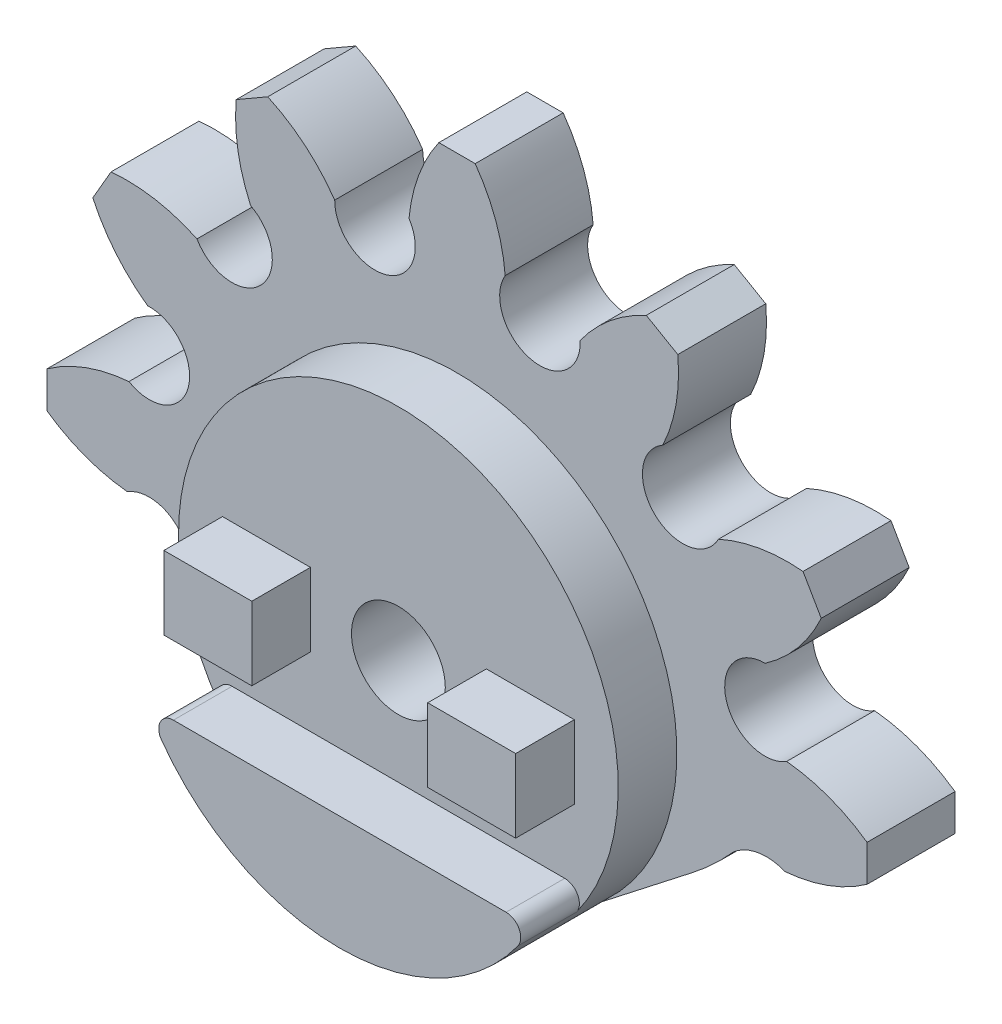
SolidWorks part; units mm, degrees
material "PLA"
ref_plane "Front Plane" through (0, 0, 0) normal (0, 0, 1) x (1, 0, 0)
ref_plane "Top Plane" through (0, 0, 0) normal (0, 1, 0) x (1, 0, 0)
ref_plane "Right Plane" through (0, 0, 0) normal (1, 0, 0) x (0, 0, -1)
other "Graphic1"
other "Graphic (Closed) -1"
sketch "Sketch1" plane through (0, 0, 0) normal (0, 0, 1) x (1, 0, 0)
  line L0 (0.1538, 8.164) -> (0.1538, 6.9226)
  line L1 (6.1332, 4.2732) -> (9.5312, 1.6264)
  line L2 (2.3379, 15.0739) -> (1.7172, 13.9988)
  line L3 (7.6844, 19.966) -> (6.6093, 19.3453)
  line L4 (14.7607, 21.5295) -> (13.5193, 21.5295)
  line L5 (21.6707, 19.3453) -> (20.5956, 19.966)
  line L6 (26.5628, 13.9988) -> (25.9421, 15.0739)
  line L7 (28.1262, 6.9226) -> (28.1262, 8.164)
  line L9 (22.1468, 4.2732) -> (18.7488, 1.6264)
  line L13 (1.7172, 1.0877) -> (2.3379, 0.0126) [skipped]
  line L14 (6.6093, -4.2588) -> (7.6844, -4.8795) [skipped]
  line L15 (20.5956, -4.8795) -> (21.6707, -4.2588) [skipped]
  line L16 (25.9421, 0.0126) -> (26.5628, 1.0877) [skipped]
  line L17 (13.5193, -6.443) -> (14.7607, -6.443) [skipped]
  circle A0 centre (14.14, 7.5433) radius 1.6
  arc A1 (9.5312, 1.6264) -> (18.7488, 1.6264) centre (14.14, 7.5433) ccw
  arc A2 (0.1538, 6.9226) -> (2.9496, 5.9002) centre (3.4462, 11.5926) ccw
  arc A3 (2.9496, 5.9002) -> (4.7183, 5.5952) centre (3.5857, 4.3084) cw
  arc A4 (4.7183, 5.5952) -> (6.1332, 4.2732) centre (12.2208, 12.2067) ccw
  arc A5 (0.1538, 8.164) -> (2.9496, 9.1863) centre (3.4106, 3.5913) cw
  arc A6 (2.9496, 9.1863) -> (3.5736, 11.7455) centre (3.644, 10.3727) ccw
  arc A7 (5.2703, 14.5613) -> (7.0904, 16.4657) centre (6.4649, 15.2416) ccw
  arc A8 (2.3379, 15.0739) -> (5.2703, 14.5613) centre (2.8721, 9.4855) cw
  arc A9 (1.7172, 13.9988) -> (3.6273, 11.7156) centre (6.9036, 16.397) ccw
  arc A10 (9.9677, 18.0559) -> (12.4961, 18.7951) centre (11.3423, 18.0478) ccw
  arc A11 (7.6844, 19.966) -> (9.9677, 18.0559) centre (5.3528, 14.8592) cw
  arc A12 (6.6093, 19.3453) -> (7.1219, 16.4129) centre (12.3, 18.829) ccw
  arc A13 (15.783, 18.7336) -> (18.3422, 18.1096) centre (16.9694, 18.0393) ccw
  arc A14 (14.7607, 21.5295) -> (15.783, 18.7336) centre (10.1881, 18.2727) cw
  arc A15 (13.5193, 21.5295) -> (12.497, 18.7336) centre (18.1894, 18.237) ccw
  arc A16 (21.1581, 16.4129) -> (23.0624, 14.5929) centre (21.8384, 15.2184) ccw
  arc A17 (21.6707, 19.3453) -> (21.1581, 16.4129) centre (16.0822, 18.8112) cw
  arc A18 (20.5956, 19.966) -> (18.3123, 18.0559) centre (22.9937, 14.7797) ccw
  arc A19 (24.6527, 11.7156) -> (25.3919, 9.1872) centre (24.6445, 10.3409) ccw
  arc A20 (26.5628, 13.9988) -> (24.6527, 11.7156) centre (21.456, 16.3304) cw
  arc A21 (25.9421, 15.0739) -> (23.0097, 14.5613) centre (25.4258, 9.3833) ccw
  arc A22 (24.6957, 3.3405) -> (24.7064, 3.341) centre (24.636, 4.7139) ccw
  arc A23 (28.1262, 6.9226) -> (25.3304, 5.9002) centre (24.8694, 11.4952) cw
  arc A24 (28.1262, 8.164) -> (25.3304, 9.1863) centre (24.8338, 3.4939) ccw
  arc A25 (21.1802, -1.3743) -> (21.1896, -1.3792) centre (21.8151, -0.1551) ccw
  arc A26 (23.5617, 5.5952) -> (22.1468, 4.2732) centre (16.0592, 12.2067) cw
  arc A27 (24.6957, 3.3405) -> (24.6527, 3.371) centre (21.3764, -1.3105) ccw
  arc A28 (15.7782, -3.6997) -> (15.7839, -3.7086) centre (16.9377, -2.9613) ccw
  arc A29 (25.3304, 5.9002) -> (23.5617, 5.5952) centre (24.6943, 4.3084) ccw
  arc A30 (21.1802, -1.3743) -> (21.1581, -1.3264) centre (15.98, -3.7425) ccw
  arc A31 (9.9373, -3.0125) -> (9.9378, -3.0231) centre (11.3106, -2.9528) ccw
  arc A33 (15.7782, -3.6997) -> (15.783, -3.6471) centre (10.0906, -3.1505) ccw
  arc A34 (5.2224, 0.5031) -> (5.2176, 0.4936) centre (6.4416, -0.1319) ccw
  arc A36 (9.9373, -3.0125) -> (9.9677, -2.9694) centre (5.2863, 0.3068) ccw
  arc A37 (4.7111, 5.6016) -> (2.8881, 5.8993) centre (3.6355, 4.7456) ccw
  arc A39 (5.2224, 0.5031) -> (5.2703, 0.5252) centre (2.8542, 5.7032) ccw
  arc A40 (1.7172, 1.0877) -> (3.6273, 3.371) centre (6.824, -1.2439) cw [skipped]
  arc A41 (6.6093, -4.2588) -> (7.1219, -1.3264) centre (12.1978, -3.7246) cw [skipped]
  arc A42 (13.5193, -6.443) -> (12.497, -3.6471) centre (18.0919, -3.1861) cw [skipped]
  arc A43 (20.5956, -4.8795) -> (18.3123, -2.9694) centre (22.9272, 0.2273) cw [skipped]
  arc A44 (25.9421, 0.0126) -> (23.0097, 0.5252) centre (25.4079, 5.601) cw [skipped]
  point P119 (14.14, 7.5433)
  dimension "D1" = 12
extrude "Boss-Extrude1" add sketch "Sketch1" along normal blind 3 contours A37 A3 A4 L1 A1 L9 A26 A29 A23 L7 A24 A19 A20 L6 A21 A16 A17 L5 A18 A13 A14 L4 A15 A10 A11 L3 A12 A7 A8 L2 A9 A6 A5 L0 A2 A0
sketch "Sketch2" plane through (0, 0, 3) normal (0, 0, 1) x (1, 0, 0)
  circle A0 centre (14.14, 7.5433) radius 7.5
  circle A1 centre (14.14, 7.5433) radius 1.6
extrude "Boss-Extrude2" add sketch "Sketch2" along normal blind 2 contours A0
sketch "Sketch3" plane through (0, 0, 5) normal (0, 0, 1) x (1, 0, 0)
  line L1 (8.14, 8.7933) -> (11.14, 8.7933)
  line L2 (8.14, 8.7933) -> (8.14, 6.2933)
  line L3 (8.14, 6.2933) -> (11.14, 6.2933)
  line L4 (11.14, 8.7933) -> (11.14, 6.2933)
  line L5 (17.14, 8.7933) -> (20.14, 8.7933)
  line L6 (17.14, 8.7933) -> (17.14, 6.2933)
  line L7 (17.14, 6.2933) -> (20.14, 6.2933)
  line L8 (20.14, 8.7933) -> (20.14, 6.2933)
  line L10 (14.14, 3.9433) -> (20.7195, 3.9433) construction
  line L11 (7.5605, 3.9433) -> (20.7195, 3.9433)
  circle A1 centre (14.14, 7.5433) radius 1.6
  arc A2 (7.5605, 3.9433) -> (20.7195, 3.9433) centre (14.14, 7.5433) ccw
  point P26 (14.14, 3.9433)
extrude "Boss-Extrude3" add sketch "Sketch3" along normal blind 2 contours L2 L1 L4 L3 | A2 L11 | L6 L5 L8 L7
fillet "Fillet1" radius 0.5 1 edges at (20.7195, 3.9433, 6)
fillet "Fillet2" radius 0.5 1 edges at (7.5605, 3.9433, 6)
